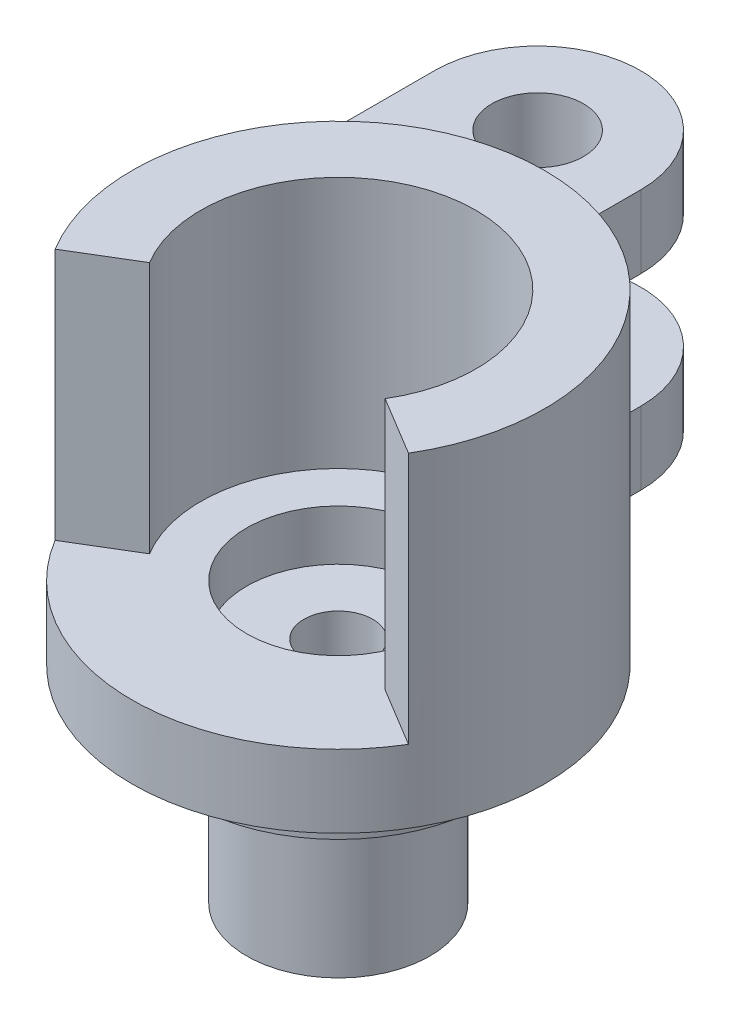
SolidWorks part; units mm, degrees
ref_plane "Front Plane" through (0, 0, 0) normal (0, 0, 1) x (1, 0, 0)
ref_plane "Top Plane" through (0, 0, 0) normal (0, 1, 0) x (1, 0, 0)
ref_plane "Right Plane" through (0, 0, 0) normal (1, 0, 0) x (0, 0, -1)
sketch "Sketch1" plane through (0, 0, 0) normal (0, 1, 0) x (1, 0, 0)
  circle A0 centre (0, 0) radius 9
  dimension "D1" = 18
extrude "Boss-Extrude1" add sketch "Sketch1" along normal blind 3.175
sketch "Sketch2" plane through (0, 3.175, 0) normal (0, 1, 0) x (1, 0, 0)
  line L0 (-7.7077, -4.6466) -> (-5.1385, -3.0978)
  line L1 (-7.7077, -4.6466) -> (7.7077, -4.6466) construction
  line L3 (5.1385, -3.0978) -> (7.7077, -4.6466)
  arc A0 (-7.7077, -4.6466) -> (7.7077, -4.6466) centre (0, 0) cw
  circle A1 centre (0, 0) radius 9 construction
  arc A2 (-5.1385, -3.0978) -> (5.1385, -3.0978) centre (0, 0) cw
  dimension "D1" = 117.832
  dimension "D2" = 3
extrude "Boss-Extrude2" add sketch "Sketch2" along normal blind 11
sketch "Sketch3" plane through (0, 0, 0) normal (0, -1, 0) x (1, 0, 0)
  circle A0 centre (0, 0) radius 6.5
  dimension "D1" = 13
extrude "Boss-Extrude3" add sketch "Sketch3" along normal blind 2
sketch "Sketch4" plane through (0, -2, 0) normal (0, -1, 0) x (1, 0, 0)
  circle A0 centre (0, 0) radius 4
  dimension "D1" = 8
extrude "Boss-Extrude4" add sketch "Sketch4" along normal blind 7
sketch "Sketch6" plane through (0, 0, 0) normal (0, 1, 0) x (1, 0, 0)
  line L0 (-9, 0) -> (-9, 13.1942)
  line L1 (0, 9) -> (0, 13.1942)
  arc A0 (7.7077, -4.6466) -> (-7.7077, -4.6466) centre (0, 0) ccw construction
  arc A1 (0, 13.1942) -> (-9, 13.1942) centre (-4.5, 13.1942) ccw
  arc A2 (0, 9) -> (-9, 0) centre (0, 0) ccw
  point P10 (-4.5, 17.6942)
  dimension "D1" = 8.6942
extrude "Boss-Extrude5" add sketch "Sketch6" along normal up to surface (3.175 mm away) up to face at (0, 3.175, 2.6861)
ref_plane "Plane1" through (0, 8.175, 0) normal (0, 1, 0) x (1, 0, 0)
sketch "Sketch7" plane through (0, 8.175, 0) normal (0, 1, 0) x (1, 0, 0)
  line L0 (0, 9) -> (0, 13.1942) construction
  line L1 (-9, 13.1942) -> (-9, 0) construction
  line L2 (0, 9) -> (0, 13.1942)
  line L3 (-9, 13.1942) -> (-9, 0)
  arc A0 (0, 9) -> (-9, 0) centre (0, 0) ccw construction
  arc A1 (0, 13.1942) -> (-9, 13.1942) centre (-4.5, 13.1942) ccw construction
  arc A2 (0, 9) -> (-9, 0) centre (0, 0) ccw
  arc A3 (0, 13.1942) -> (-9, 13.1942) centre (-4.5, 13.1942) ccw
extrude "Boss-Extrude7" add sketch "Sketch7" along normal blind 3.175
sketch "Sketch8" plane through (0, 11.35, 0) normal (0, 1, 0) x (1, 0, 0)
  circle A0 centre (-4.5, 13.1942) radius 2
  arc A1 (0, 13.1942) -> (-9, 13.1942) centre (-4.5, 13.1942) ccw construction
  dimension "D1" = 4
extrude "Cut-Extrude1" cut sketch "Sketch8" against normal up to surface (11.35 mm away) up to face at (0, 0, -6.5)
sketch "Sketch9" plane through (0, 3.175, 0) normal (0, 1, 0) x (1, 0, 0)
  circle A0 centre (0, 0) radius 1.5
  dimension "D1" = 3
extrude "Cut-Extrude2" cut sketch "Sketch9" against normal up to surface (12.175 mm away) contours A0 up to face at (0, -9, -4)
sketch "Sketch10" plane through (0, 3.175, 0) normal (0, 1, 0) x (1, 0, 0)
  circle A0 centre (0, 0) radius 4
  dimension "D1" = 8
extrude "Cut-Extrude3" cut sketch "Sketch10" against normal blind 2.2
